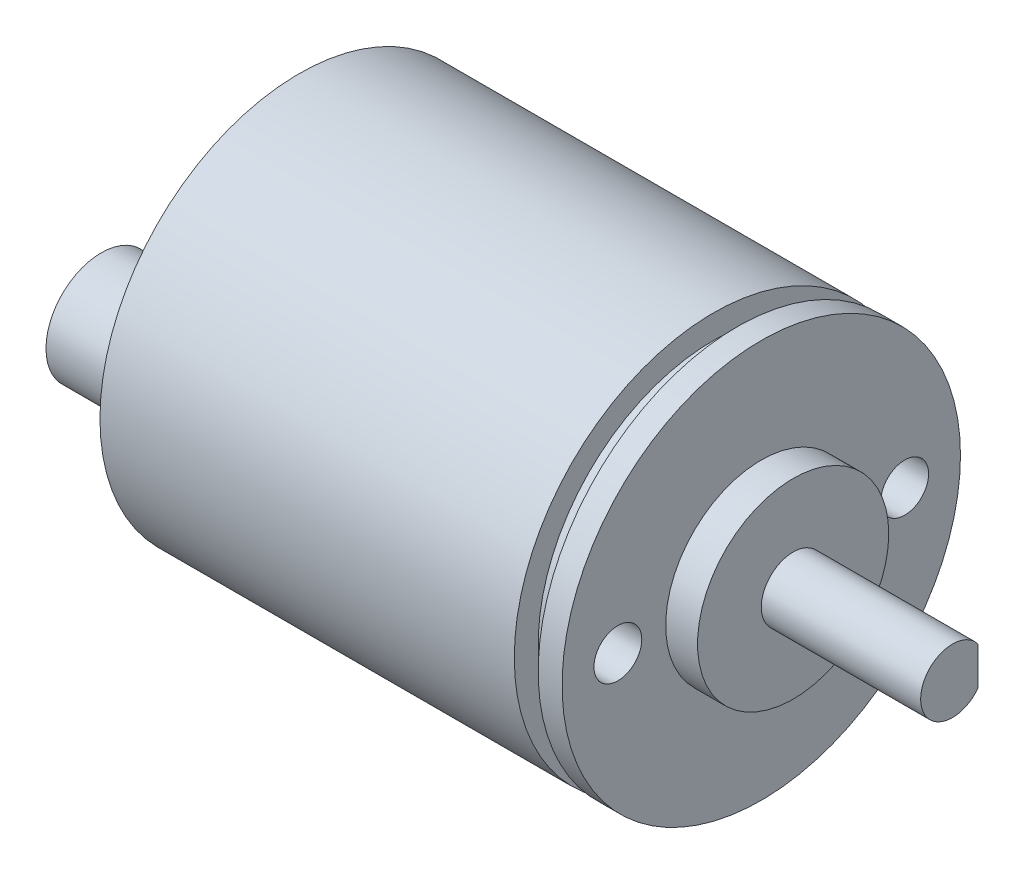
SolidWorks part; units mm, degrees
ref_plane "Front Plane" through (0, 0, 0) normal (0, 0, 1) x (1, 0, 0)
ref_plane "Top Plane" through (0, 0, 0) normal (0, 1, 0) x (1, 0, 0)
ref_plane "Right Plane" through (0, 0, 0) normal (1, 0, 0) x (0, 0, -1)
sketch "Sketch1" plane through (0, 0, 0) normal (1, 0, 0) x (0, 0, -1)
  circle A0 centre (0, 0) radius 12.5
  dimension "D1" = 25
extrude "Boss-Extrude1" add sketch "Sketch1" along normal blind 26
sketch "Sketch2" plane through (26, 0, 0) normal (1, 0, 0) x (0, 0, -1)
  circle A0 centre (0, 0) radius 11
  dimension "D1" = 22
extrude "Boss-Extrude2" add sketch "Sketch2" along normal blind 1.5
sketch "Sketch3" plane through (27.5, 0, 0) normal (1, 0, 0) x (0, 0, -1)
  circle A0 centre (0, 0) radius 12.5
  dimension "D1" = 25
extrude "Boss-Extrude3" add sketch "Sketch3" along normal blind 1.5
sketch "Sketch4" plane through (29, 0, 0) normal (1, 0, 0) x (0, 0, -1)
  circle A0 centre (0, 0) radius 6
  dimension "D1" = 12
extrude "Boss-Extrude4" add sketch "Sketch4" along normal blind 2
sketch "Sketch5" plane through (31, 0, 0) normal (1, 0, 0) x (0, 0, -1)
  circle A0 centre (0, 0) radius 2
  dimension "D1" = 4
extrude "Boss-Extrude5" add sketch "Sketch5" along normal blind 10
sketch "Sketch6" plane through (41, 0, 0) normal (1, 0, 0) x (0, 0, -1)
  line L1 (1.6, 3.2717) -> (4.2374, 3.2717)
  line L2 (1.6, 3.2717) -> (1.6, -3.3926)
  line L3 (1.6, -3.3926) -> (4.2374, -3.3926)
  line L4 (4.2374, 3.2717) -> (4.2374, -3.3926)
  circle A0 centre (0, 0) radius 2 construction
  dimension "D1" = 1.6
extrude "Cut-Extrude1" cut sketch "Sketch6" against normal blind 8
sketch "Sketch8" plane through (29, 0, 0) normal (1, 0, 0) x (0, 0, -1)
  circle A0 centre (9, 0) radius 1.5
  circle A1 centre (0, 0) radius 6 construction
  circle A2 centre (-9, 0) radius 1.5
  point P5 (0, 0)
  dimension "D1" = 3
  dimension "D2" = 9
  dimension "D3" = 2
extrude "Cut-Extrude2" cut sketch "Sketch8" against normal blind 6.35
sketch "Sketch9" plane through (0, 0, 0) normal (-1, 0, 0) x (0, 0, 1)
  circle A0 centre (6.9146, 0) radius 3.4714
extrude "Boss-Extrude6" add sketch "Sketch9" along normal blind 5.5
